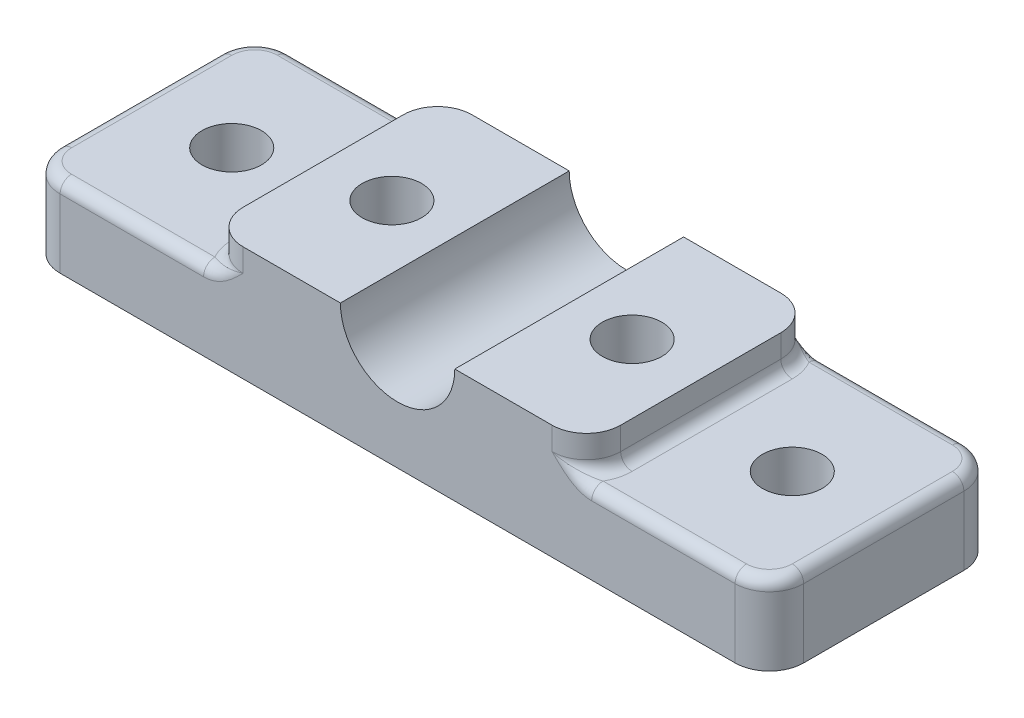
SolidWorks part; units mm, degrees
material "ABS"
ref_plane "Front Plane" through (0, 0, 0) normal (0, 0, 1) x (1, 0, 0)
ref_plane "Top Plane" through (0, 0, 0) normal (0, 1, 0) x (1, 0, 0)
ref_plane "Right Plane" through (0, 0, 0) normal (1, 0, 0) x (0, 0, -1)
sketch "Sketch1" plane through (0, 0, 0) normal (0, 1, 0) x (1, 0, 0)
  line L0 (-50.7915, 0) -> (50.7915, 0) construction
  line L1 (0, 10) -> (0, -10) construction
  line L2 (-29.5, -10) -> (29.5, -10)
  line L3 (-32.5, -7) -> (-32.5, 7)
  line L4 (-29.5, 10) -> (29.5, 10)
  line L5 (32.5, -7) -> (32.5, 7)
  line L6 (-32.5, -10) -> (32.5, 10) construction
  line L7 (-32.5, 10) -> (32.5, -10) construction
  line L8 (-16.5, -10) -> (16.5, -10) construction
  line L9 (-16.5, -10) -> (-16.5, 10) construction
  line L10 (-16.5, 10) -> (16.5, 10) construction
  line L11 (16.5, -10) -> (16.5, 10) construction
  line L12 (-16.5, -10) -> (16.5, 10) construction
  line L13 (-16.5, 10) -> (16.5, -10) construction
  arc A0 (-32.5, -7) -> (-29.5, -10) centre (-29.5, -7) ccw
  arc A1 (29.5, -10) -> (32.5, -7) centre (29.5, -7) ccw
  arc A2 (32.5, 7) -> (29.5, 10) centre (29.5, 7) ccw
  arc A3 (-29.5, 10) -> (-32.5, 7) centre (-29.5, 7) ccw
  circle A4 centre (-10.5, 0) radius 2.6
  circle A5 centre (-24.5, 0) radius 2.6
  circle A6 centre (24.5, 0) radius 2.6
  circle A7 centre (10.5, 0) radius 2.6
  point P3 (0, 0)
  point P4 (0, 0)
  point P25 (0, 0)
  dimension "D3" = 3
  dimension "D4" = 5.2
  dimension "D7" = 14
  dimension "D1" = 65
  dimension "D2" = 20
  dimension "D5" = 33
  dimension "D6" = 10.5
extrude "Boss-Extrude1" add sketch "Sketch1" along normal blind 7
sketch "Sketch2" plane through (0, 7, 0) normal (0, 1, 0) x (1, 0, 0)
  line L0 (29.5, 10) -> (-29.5, 10) construction
  line L1 (-13.5, -10) -> (13.5, -10)
  line L2 (-16.5, -7) -> (-16.5, 7)
  line L3 (-13.5, 10) -> (13.5, 10)
  line L4 (16.5, -7) -> (16.5, 7)
  line L5 (-16.5, -10) -> (16.5, 10) construction
  line L6 (-16.5, 10) -> (16.5, -10) construction
  arc A0 (13.5, 10) -> (16.5, 7) centre (13.5, 7) cw
  arc A1 (16.5, -7) -> (13.5, -10) centre (13.5, -7) cw
  arc A2 (-13.5, -10) -> (-16.5, -7) centre (-13.5, -7) cw
  arc A3 (-16.5, 7) -> (-13.5, 10) centre (-13.5, 7) cw
  circle A4 centre (-10.5, 0) radius 2.6 construction
  circle A5 centre (10.5, 0) radius 2.6 construction
  circle A6 centre (-10.5, 0) radius 2.6
  circle A7 centre (10.5, 0) radius 2.6
  point P0 (0, 0)
  dimension "D2" = 3
  dimension "D1" = 33
extrude "Boss-Extrude2" add sketch "Sketch2" along normal blind 3
sketch "Sketch3" plane through (0, 0, 10) normal (0, 0, 1) x (1, 0, 0)
  line L0 (0, 0) -> (0, 16.2371) construction
  line L1 (-29.5, 0) -> (29.5, 0) construction
  circle A0 centre (0, 10) radius 5
  dimension "D1" = 10
  dimension "D2" = 10
extrude "Cut-Extrude1" cut sketch "Sketch3" against normal up to surface (20 mm away) up to face at (2, 6.375, -10)
sketch "Sketch4" plane through (0, 0, 0) normal (0, -1, 0) x (1, 0, 0)
  line L0 (-32.5, -7) -> (-32.5, 7) construction
  line L1 (-10.5, 4.6188) -> (-14.5, 2.3094)
  line L2 (-14.5, 2.3094) -> (-14.5, -2.3094)
  line L3 (-14.5, -2.3094) -> (-10.5, -4.6188)
  line L4 (-10.5, -4.6188) -> (-6.5, -2.3094)
  line L5 (-6.5, -2.3094) -> (-6.5, 2.3094)
  line L6 (-6.5, 2.3094) -> (-10.5, 4.6188)
  line L7 (14.5, 2.3094) -> (10.5, 4.6188)
  line L8 (10.5, 4.6188) -> (6.5, 2.3094)
  line L9 (6.5, 2.3094) -> (6.5, -2.3094)
  line L10 (6.5, -2.3094) -> (10.5, -4.6188)
  line L11 (10.5, -4.6188) -> (14.5, -2.3094)
  line L12 (14.5, -2.3094) -> (14.5, 2.3094)
  line L13 (32.5, 7) -> (32.5, -7) construction
  circle A0 centre (-10.5, 0) radius 4 construction
  circle A1 centre (10.5, 0) radius 4 construction
  dimension "D1" = 8
extrude "Cut-Extrude2" cut sketch "Sketch4" against normal blind 5
fillet "Fillet1" radius 1 16 edges at (-16.5, 7, 0) (16.5, 7, 0) (31.6213, 7, -9.1213) (32.5, 7, 0) (-31.6213, 7, -9.1213) (-32.5, 7, 0) (31.6213, 7, 9.1213) (-31.6213, 7, 9.1213)
